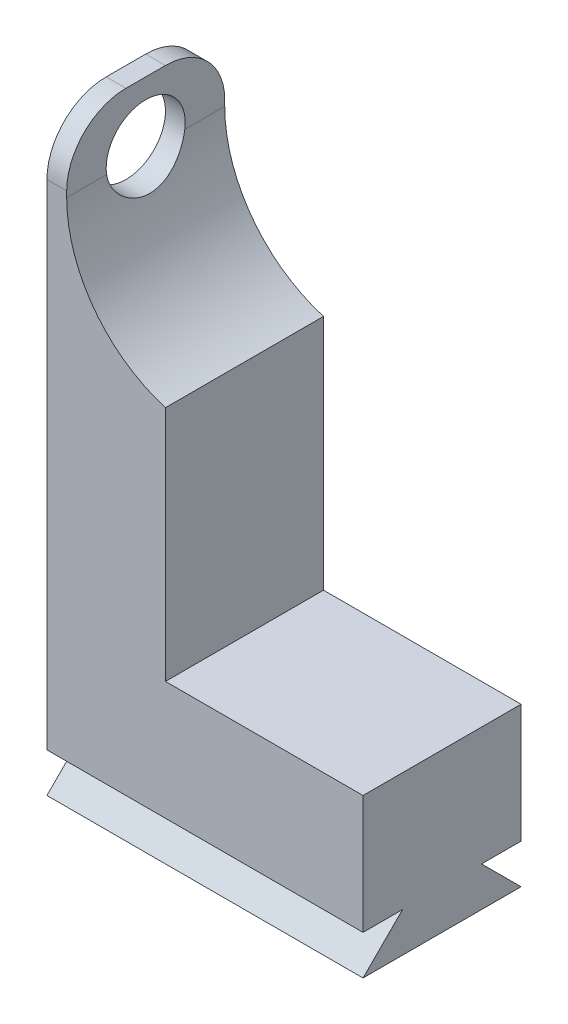
SolidWorks part; units mm, degrees
ref_plane "Front Plane" through (0, 0, 0) normal (0, 0, 1) x (1, 0, 0)
ref_plane "Top Plane" through (0, 0, 0) normal (0, 1, 0) x (1, 0, 0)
ref_plane "Right Plane" through (0, 0, 0) normal (1, 0, 0) x (0, 0, -1)
sketch "Sketch1" plane through (0, 0, 0) normal (1, 0, 0) x (0, 0, -1)
  line L1 (-4, -15) -> (4, -15)
  line L2 (-4, -15) -> (-4, 15)
  line L3 (-4, 15) -> (4, 15)
  line L4 (4, -15) -> (4, 15)
  line L5 (-4, -15) -> (4, 15) construction
  line L6 (-4, 15) -> (4, -15) construction
  point P0 (0, 0)
extrude "Boss-Extrude1" add sketch "Sketch1" along normal blind 6
sketch "Sketch2" plane through (6, 0, 0) normal (1, 0, 0) x (0, 0, -1)
  line L0 (-4, 15) -> (-4, -15) construction
  line L1 (4, 15) -> (-4, 15)
  line L2 (4, 15) -> (4, 5)
  line L3 (4, 5) -> (-4, 5)
  line L4 (-4, 15) -> (-4, 5)
extrude "Cut-Extrude1" cut sketch "Sketch2" against normal blind 5
sketch "Sketch3" plane through (0, 0, 0) normal (-1, 0, 0) x (0, 0, 1)
  line L0 (0, 15) -> (0, 12) construction
  line L1 (-4, 15) -> (4, 15) construction
  circle A0 centre (0, 12) radius 2
extrude "Cut-Extrude2" cut sketch "Sketch3" against normal up to next
fillet "Fillet1" radius 3 2 edges at (0.5, 15, -4) (0.5, 15, 4)
fillet "Fillet2" radius 7 1 edges at (1, 5, 0)
sketch "Sketch4" plane through (6, 0, 0) normal (1, 0, 0) x (0, 0, -1)
  line L0 (-4, 5) -> (-4, -15) construction
  line L1 (4, -15) -> (-4, -15)
  line L2 (4, -15) -> (4, -7)
  line L3 (4, -7) -> (-4, -7)
  line L4 (-4, -15) -> (-4, -7)
extrude "Boss-Extrude2" add sketch "Sketch4" along normal blind 10
sketch "Sketch6" plane through (0, 0, 0) normal (-1, 0, 0) x (0, 0, 1)
  line L0 (4, -15) -> (4, -13)
  line L1 (4, 12) -> (4, -15) construction
  line L2 (4, -13) -> (2, -13)
  line L3 (2, -13) -> (4, -15)
  line L4 (-4, -15) -> (-4, -13)
  line L5 (-4, -15) -> (-4, 12) construction
  line L6 (-4, -13) -> (-2, -13)
  line L7 (-2, -13) -> (-4, -15)
extrude "Cut-Extrude4" cut sketch "Sketch6" against normal up to next
